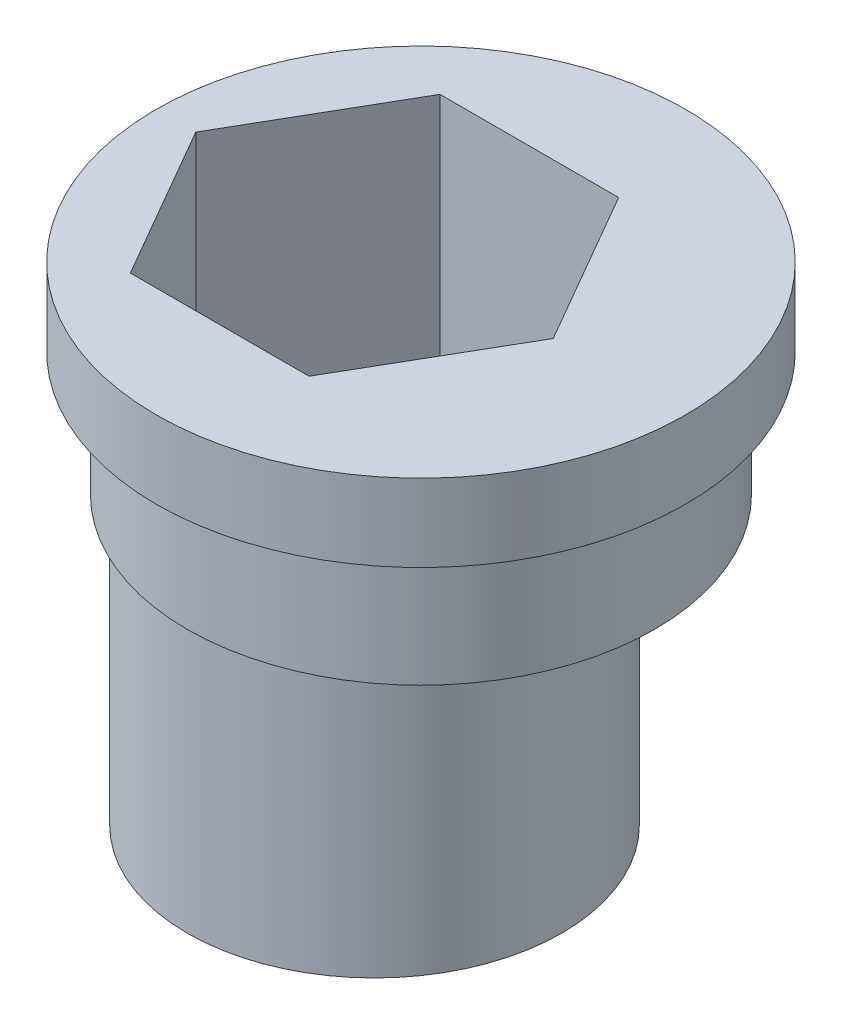
SolidWorks part; units mm, degrees
ref_plane "Front Plane" through (0, 0, 0) normal (0, 0, 1) x (1, 0, 0)
ref_plane "Top Plane" through (0, 0, 0) normal (0, 1, 0) x (1, 0, 0)
ref_plane "Right Plane" through (0, 0, 0) normal (1, 0, 0) x (0, 0, -1)
sketch "Sketch1" plane through (0, 0, 0) normal (0, 1, 0) x (1, 0, 0)
  line L0 (0, 0) -> (1.5, 0) construction
  line L1 (2.8868, 5) -> (-2.8868, 5)
  line L2 (-2.8868, 5) -> (-5.7735, 0)
  line L3 (-5.7735, 0) -> (-2.8868, -5)
  line L4 (-2.8868, -5) -> (2.8868, -5)
  line L5 (2.8868, -5) -> (5.7735, 0)
  line L6 (5.7735, 0) -> (2.8868, 5)
  circle A0 centre (0, 0) radius 5 construction
  circle A1 centre (0, 0) radius 6.05
  circle A2 centre (1.5, 0) radius 7.55
  circle A3 centre (1.5, 0) radius 8.55
  point P13 (0, 0)
  dimension "D2" = 15.1
  dimension "12.1" = 12.1
  dimension "D3" = 17.1
  dimension "D1" = 10
  dimension "D4" = 1.5
extrude "Boss-Extrude1" add sketch "Sketch1" against normal blind 10 contours A1 L6 L5 L4 L3 L2 L1 region at (0, 0, 5.8789)
extrude "Boss-Extrude2" add sketch "Sketch1<3>" along normal blind 4 contours A1 A2 | A1 L6 L5 L4 L3 L2 L1 region at (0, 0, 5.8789) region at (1.5, 0, -7.3365)
sketch "Sketch1<3>" plane through (0, 0, 0) normal (0, 1, 0) x (1, 0, 0) same geometry as "Sketch1"
extrude "Boss-Extrude3" add sketch "Sketch1<5>" along normal blind 2.5 from surface contours A1 L6 L5 L4 L3 L2 L1 | A1 A2 | A3 A2 region at (0, 0, 5.8789) region at (1.5, 0, -7.3365) region at (-6.8082, 0, 0) starting at face at (1.5, 4, 7.55)
sketch "Sketch1<5>" plane through (0, 0, 0) normal (0, 1, 0) x (1, 0, 0) same geometry as "Sketch1"
